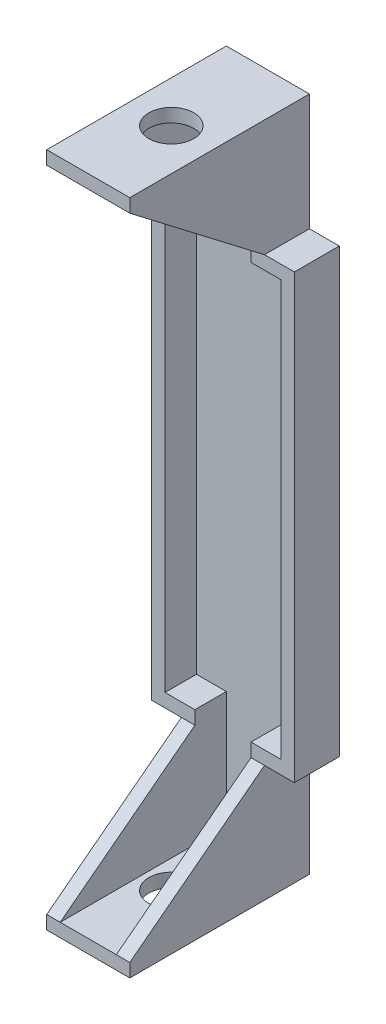
SolidWorks part; units mm, degrees
material "6061-T6 (SS)"
ref_plane "Front Plane" through (0, 0, 0) normal (0, 0, 1) x (1, 0, 0)
ref_plane "Top Plane" through (0, 0, 0) normal (0, 1, 0) x (1, 0, 0)
ref_plane "Right Plane" through (0, 0, 0) normal (1, 0, 0) x (0, 0, -1)
sketch "Sketch16" plane through (0, 0, 0) normal (0, 0, 1) x (1, 0, 0)
  line L0 (0, 37.625) -> (0, -37.625) construction
  line L1 (-15.9, -37.625) -> (15.9, -37.625)
  line L2 (-15.9, -37.625) -> (-15.9, 11.625)
  line L3 (-9.25, 37.625) -> (9.25, 37.625)
  line L4 (15.9, -37.625) -> (15.9, 11.625)
  line L5 (-15.9, -37.625) -> (9.25, 21.8888) construction
  line L6 (-9.25, 21.8888) -> (15.9, -37.625) construction
  line L7 (9.25, 37.625) -> (9.25, 11.625)
  line L8 (9.25, 11.625) -> (15.9, 11.625)
  line L9 (-9.25, 11.625) -> (-15.9, 11.625)
  line L10 (-9.25, 37.625) -> (-9.25, 11.625)
  point P0 (0, 0)
  dimension "D2" = 31.8
  dimension "D3" = 9.25
  dimension "D4" = 26
extrude "Boss-Extrude11" add sketch "Sketch16" along normal blind 40
sketch "Sketch17" plane through (0, 0, 40) normal (0, 0, 1) x (1, 0, 0)
  line L0 (-9.25, 34.625) -> (9.25, 34.625) construction
  line L1 (-9.25, 37.625) -> (-9.25, 11.625) construction
  line L2 (9.25, 11.625) -> (9.25, 37.625) construction
  line L3 (9.25, 37.625) -> (-9.25, 37.625) construction
  line L5 (-20.3701, 34.625) -> (26.8551, 34.625)
  line L6 (-20.3701, 34.625) -> (-20.3701, -50.5561)
  line L7 (-20.3701, -50.5561) -> (26.8551, -50.5561)
  line L8 (26.8551, 34.625) -> (26.8551, -50.5561)
  dimension "D1" = 3
extrude "Cut-Extrude6" cut sketch "Sketch17" against normal blind 30
shell "Shell3" thickness 3 removed face at (0, -37.625, 5) removed face at (0, 5.0625, 10)
sketch "Sketch18" plane through (0, 0, 40) normal (0, 0, 1) x (1, 0, 0)
  line L0 (0, 34.625) -> (0, 37.625) construction
  line L1 (9.25, 34.625) -> (-9.25, 34.625) construction
  line L2 (9.25, 37.625) -> (-9.25, 37.625) construction
  line L4 (0, 37.625) -> (-54.4717, 37.625)
  line L5 (0, 37.625) -> (0, -109.748)
  line L6 (0, -109.748) -> (-54.4717, -109.748)
  line L7 (-54.4717, 37.625) -> (-54.4717, -109.748)
extrude "Cut-Extrude7" cut sketch "Sketch18" against normal blind 308
sketch "Sketch19" plane through (9.25, 0, 0) normal (1, 0, 0) x (0, 0, -1)
  line L0 (-40, 34.625) -> (-10, 11.625)
  line L1 (-10, 11.625) -> (-10, 34.625)
  line L2 (-10, 34.625) -> (-40, 34.625)
extrude "Boss-Extrude12" add sketch "Sketch19" against normal blind 3
sketch "Sketch20" plane through (6.25, 0, 0) normal (-1, 0, 0) x (0, 0, 1)
  line L0 (3, 34.625) -> (8, 34.625)
  line L1 (40, 34.625) -> (3, 34.625) construction
  line L2 (8, 34.625) -> (3, 31.625)
  line L3 (3, 8.625) -> (3, 34.625) construction
  line L4 (3, 31.625) -> (3, 34.625)
  dimension "D1" = 3
  dimension "D2" = 5
extrude "Boss-Extrude13" add sketch "Sketch20" along normal blind 2
mirror "Mirror3" about plane through (0, 37.625, -268) normal (1, 0, 0) of bodies 122
mirror "Mirror4" about plane through (-15.9, -37.625, 40) normal (0, 1, 0) of bodies 123
sketch "Sketch21" plane through (0, 34.625, 0) normal (0, -1, 0) x (1, 0, 0)
  line L0 (0, 3) -> (0, 40) construction
  line L1 (4.25, 3) -> (-4.25, 3) construction
  line L2 (6.25, 40) -> (-6.25, 40) construction
  circle A0 centre (0, 21.5) radius 5
  point P6 (0, 21.5)
  dimension "D1" = 10
extrude "Cut-Extrude8" cut sketch "Sketch21" against normal through all both and the other way through all
